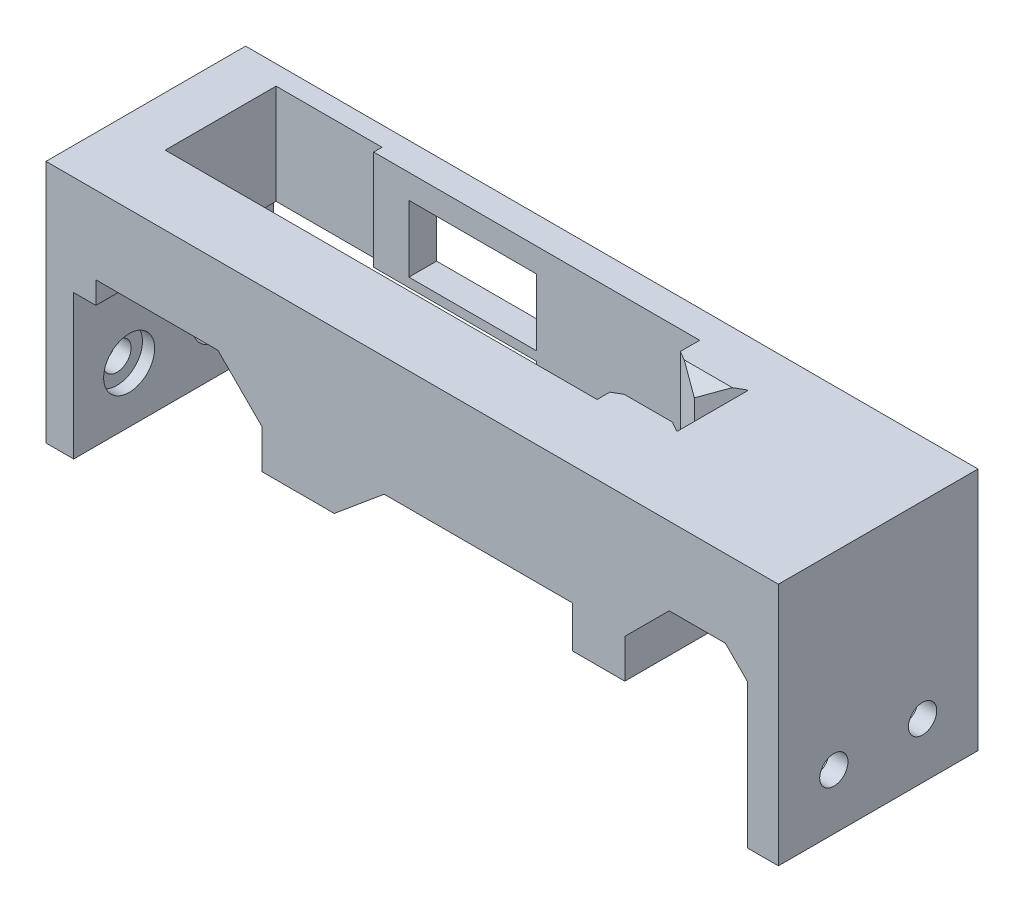
SolidWorks part; units mm, degrees
note: The reader was unsure of these and kept them because the rebuilt part matched: shared geometry of "Sketch3<4>", "Sketch11<6>", "Sketch11<7>".
ref_plane "Front Plane" through (0, 0, 0) normal (0, 0, 1) x (1, 0, 0)
ref_plane "Top Plane" through (0, 0, 0) normal (0, 1, 0) x (1, 0, 0)
ref_plane "Right Plane" through (0, 0, 0) normal (1, 0, 0) x (0, 0, -1)
sketch "Sketch1" plane through (0, 0, 0) normal (0, 1, 0) x (1, 0, 0)
  line L0 (-57.05, 14.5) -> (-57.05, -5.5)
  line L1 (66.05, 18) -> (-66.05, 18)
  line L2 (66.05, 18) -> (66.05, -18)
  line L3 (66.05, -18) -> (-66.05, -18)
  line L4 (-66.05, 18) -> (-66.05, -18)
  line L5 (66.05, 18) -> (-66.05, -18) construction
  line L6 (66.05, -18) -> (-66.05, 18) construction
  line L7 (-57.05, -5.5) -> (20.85, -5.5)
  line L8 (-57.05, 14.5) -> (-37.95, 14.5)
  line L9 (-37.95, 14.5) -> (-37.95, 13)
  line L10 (-37.95, 13) -> (20.85, 13)
  line L11 (20.85, 13) -> (20.85, 9.51)
  line L12 (20.85, -5.5) -> (20.85, -3.2)
  line L13 (20.85, 9.51) -> (33.05, 9.51) construction
  line L14 (33.05, 9.51) -> (33.05, -3.2)
  line L15 (32.85, 9.51) -> (26.85, 6.0423)
  line L16 (33.05, 9.51) -> (32.85, 9.51)
  line L17 (20.85, 9.51) -> (26.85, 6.0423)
  line L18 (20.85, -3.2) -> (26.85, 0.2677)
  line L19 (33.05, -3.2) -> (32.85, -3.2)
  line L20 (32.85, -3.2) -> (26.85, 0.2677)
  point P0 (0, 0)
  dimension "D1" = 132.1
  dimension "D2" = 36
  dimension "D3" = 9
  dimension "D4" = 12.5
  dimension "D5" = 3.5
  dimension "D6" = 5
  dimension "D7" = 19.1
  dimension "D8" = 77.9
  dimension "D9" = 3.49
  dimension "D10" = 2.3
  dimension "D11" = 33
  dimension "D12" = 6.93
  dimension "D13" = 0.2
extrude "Boss-Extrude1" add sketch "Sketch1" against normal blind 44
sketch "Sketch3" plane through (0, 0, -18) normal (0, 0, -1) x (-1, 0, 0)
  line L0 (-60.48, -44) -> (-60.48, -18)
  line L1 (-66.05, -44) -> (66.05, -44) construction
  line L2 (-60.48, -18) -> (-56.48, -14)
  line L3 (-56.48, -14) -> (-46.35, -14)
  line L4 (-46.35, -14) -> (-38.35, -22)
  line L5 (-38.35, -22) -> (-38.35, -29)
  line L6 (-38.35, -29) -> (-20.85, -29)
  line L7 (-20.85, -29) -> (-20.85, -44)
  line L8 (8.55, -18) -> (61.05, -18)
  line L9 (61.05, -18) -> (61.05, -44)
  line L10 (-66.05, -44) -> (-66.05, 0) construction
  line L11 (31.6, -4.36) -> (8.55, -4.36)
  line L12 (31.6, -4.36) -> (31.6, -16.36)
  line L13 (31.6, -16.36) -> (8.55, -16.36)
  line L14 (8.55, -4.36) -> (8.55, -16.36)
  line L16 (66.05, -44) -> (66.05, 0) construction
  line L17 (-20.85, -29) -> (8.55, -18)
  line L18 (8.55, -44) -> (8.55, 0) construction
  line L19 (-66.05, 0) -> (66.05, 0) construction
  line L20 (-60.48, -44) -> (61.05, -44)
  point P1 (-60.48, -14)
  point P6 (-38.35, -14)
  point P13 (-8.0922, -48.2439)
  line M18 (-66.05, -44) -> (66.05, -44)
  dimension "D13" = 1.64
  dimension "D1" = 5.57
  dimension "D2" = 15
  dimension "D3" = 30
  dimension "D4" = 22.13
  dimension "D5" = 26
  dimension "D6" = 5
  dimension "D9" = 52.5
  dimension "D10" = 17.5
  dimension "D11" = 23.05
  dimension "D12" = 12
extrude "Cut-Extrude1" cut sketch "Sketch3" against normal up to surface (36 mm away) contours L7 L6 L5 L4 L3 L2 L0 M18 up to face at (0, -22, 18)
extrude "Cut-Extrude2" cut sketch "Sketch3<4>" against normal up to surface (23.5 mm away) contours L17 L7 L9 L8 M18 | L11 L14 L13 L12
sketch "Sketch3<4>" plane through (0, 0, -18) normal (0, 0, -1) x (-1, 0, 0) same geometry as "Sketch3"
sketch "Sketch4" plane through (0, 0, 18) normal (0, 0, 1) x (1, 0, 0)
  line L0 (-61.05, -44) -> (-61.05, -18)
  line L1 (-66.05, -44) -> (20.85, -44) construction
  line L2 (-61.05, -18) -> (-57.05, -18)
  line L3 (-57.05, -18) -> (-57.05, -14)
  line L4 (-57.05, -14) -> (-35.05, -14)
  line L5 (-27.05, -22) -> (-27.05, -29)
  line L6 (-27.05, -29) -> (-14.05, -29)
  line L9 (-66.05, -44) -> (-66.05, 0) construction
  line L10 (38.35, -29) -> (20.85, -29) construction
  line L12 (-35.05, -14) -> (-27.05, -22)
  line L13 (-14.05, -29) -> (-5.05, -21.5)
  line L17 (20.85, -29) -> (20.85, -44)
  line L18 (20.85, -44) -> (-61.05, -44)
  line L19 (20.85, -29) -> (20.85, -21.5)
  line L23 (-5.05, -21.5) -> (20.85, -21.5)
  point P7 (-27.05, -14)
  point P10 (-14.05, -21.5)
  point P11 (0, 0)
  point P15 (20.85, -23.3065)
  point P16 (0, 0)
  point P22 (0, 0)
  point P23 (0, 0)
  dimension "D1" = 5
  dimension "D2" = 4
  dimension "D3" = 4
  dimension "D4" = 26
  dimension "D5" = 34
  dimension "D6" = 22
  dimension "D7" = 15
  dimension "D8" = 7.5
  dimension "D10" = 9
extrude "Cut-Extrude3" cut sketch "Sketch4" against normal up to surface (12.5 mm away)
sketch "Sketch7" plane through (0, -29, 0) normal (0, -1, 0) x (1, 0, 0)
  line L0 (20.85, 3.2) -> (23.35, 5.7)
  line L1 (23.35, 5.7) -> (23.35, 8)
  line L3 (38.35, 18) -> (20.85, 18) construction
  line L4 (38.35, 18) -> (38.35, -18) construction
  line L5 (28.95, 18) -> (20.85, 18)
  line L6 (20.85, 18) -> (20.85, 3.2)
  line L7 (28.95, 18) -> (29.35, 8)
  line L8 (29.35, 8) -> (23.35, 8)
  dimension "D1" = 2.5
  dimension "D2" = 2.5
  dimension "D3" = 9.4
  dimension "D4" = 10
  dimension "D5" = 6
extrude "Cut-Extrude6" cut sketch "Sketch7" against normal up to surface (7.5 mm away) up to face at (7.9, -21.5, 11.75)
sketch "Sketch10" plane through (20.85, 0, 0) normal (-1, 0, 0) x (0, 0, 1)
  line L6 (-3.155, 6.0489) -> (-3.155, -5.0392) construction
  line L7 (3.2, 0) -> (-9.51, 0) construction
  line L11 (-8.5523, 0) -> (-6.0423, 0)
  line L20 (-6.0423, 0) -> (-6.0423, -2.51)
  line L21 (-6.0423, -2.51) -> (-8.5523, 0)
  line L23 (-9.51, 0) -> (-13, 0) construction
  line L24 (-6.0423, -29) -> (-6.0423, 0) construction
  line L25 (-0.2677, 0) -> (-0.2677, -2.51)
  line L26 (2.2423, 0) -> (-0.2677, 0)
  line L27 (-0.2677, -2.51) -> (2.2423, 0)
  line L28 (-9.51, -29) -> (-6.0423, -25.5323)
  line L29 (-6.0423, -25.5323) -> (-6.0423, -29)
  line L30 (-6.0423, -29) -> (-9.51, -29)
  line L31 (-0.2677, -25.5323) -> (-0.2677, -29)
  line L32 (3.2, -29) -> (-0.2677, -25.5323)
  line L33 (-0.2677, -29) -> (3.2, -29)
  point P8 (-3.155, 0)
  dimension "D1" = 2.51
extrude "Cut-Extrude7" cut sketch "Sketch10" against normal up to surface (12.2 mm away) up to face at (33.05, -14.5, -3.155)
sketch "Sketch11" plane through (-61.05, 0, 0) normal (1, 0, 0) x (0, 0, -1)
  line L0 (-18, -44) -> (18, -44) construction
  line L1 (-18, -44) -> (-18, -18) construction
  line L2 (0, -46.5649) -> (0, -25.2614) construction
  circle A0 centre (-8, -34) radius 4.6
  circle A2 centre (-8, -34) radius 2.55
  circle A3 centre (8, -34) radius 2.55
  circle A4 centre (8, -34) radius 4.6
  dimension "D3" = 5.1
  dimension "D4" = 9.2
  dimension "D1" = 10
  dimension "D2" = 10
extrude "Cut-Extrude8" cut sketch "Sketch11" against normal up to surface and the other way up to surface contours A3 | A2 up to face at (-66.05, -22, 0) other way up to face at (66.05, -22, 0)
extrude "Cut-Extrude10" cut sketch "Sketch11<6>" against normal blind 2.2
sketch "Sketch11<6>" plane through (-61.05, 0, 0) normal (1, 0, 0) x (0, 0, -1) same geometry as "Sketch11"
extrude "Cut-Extrude11" cut sketch "Sketch11<7>" along normal blind 2.2 from surface at 121.53 starting at face at (60.48, -31, 0)
sketch "Sketch11<7>" plane through (-61.05, 0, 0) normal (1, 0, 0) x (0, 0, -1) same geometry as "Sketch11"
